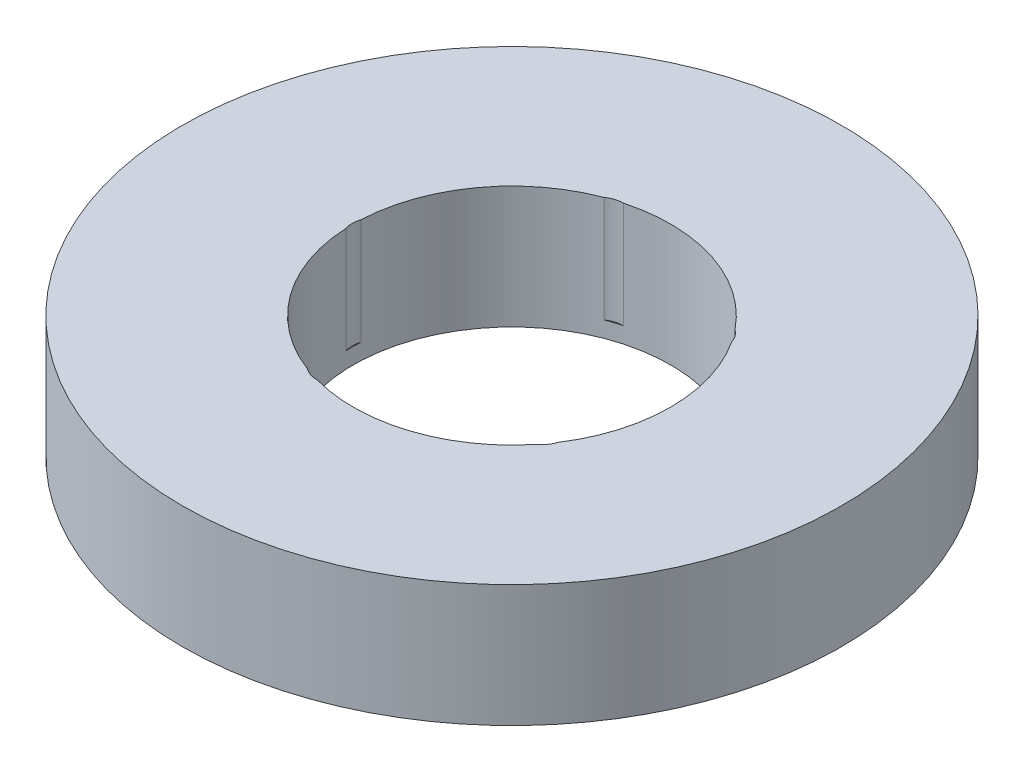
SolidWorks part; units mm, degrees
ref_plane "Front Plane" through (0, 0, 0) normal (0, 0, 1) x (1, 0, 0)
ref_plane "Top Plane" through (0, 0, 0) normal (0, 1, 0) x (1, 0, 0)
ref_plane "Right Plane" through (0, 0, 0) normal (1, 0, 0) x (0, 0, -1)
sketch "Sketch1" plane through (0, 0, 0) normal (0, 1, 0) x (1, 0, 0)
  circle A0 centre (0, 0) radius 67.5
  dimension "FLANGE_OD" = 135
extrude "Boss-Extrude1" add sketch "Sketch1" along normal blind 25
sketch "Sketch2" plane through (0, 0, 0) normal (0, 1, 0) x (1, 0, 0)
  circle A0 centre (0, 0) radius 32.5
  dimension "BORE_D" = 65
extrude "Cut-Extrude1" cut sketch "Sketch2" along normal through all
sketch "Sketch3" plane through (0, 25, 0) normal (0, 1, 0) x (1, 0, 0)
  circle A0 centre (0, 0) radius 27.7648 construction
  circle A1 centre (-27.7648, 0) radius 4.9511
  dimension "BOLT_D" = 9.9023
  dimension "BOLT_PCD" = 55.5296
extrude "Cut-Extrude2" cut sketch "Sketch3" against normal blind 21.7377
pattern_circular "CirPattern1" count 5 over 360 about axis through (0, 0, 0) along (0, 1, 0) of "Cut-Extrude2"
